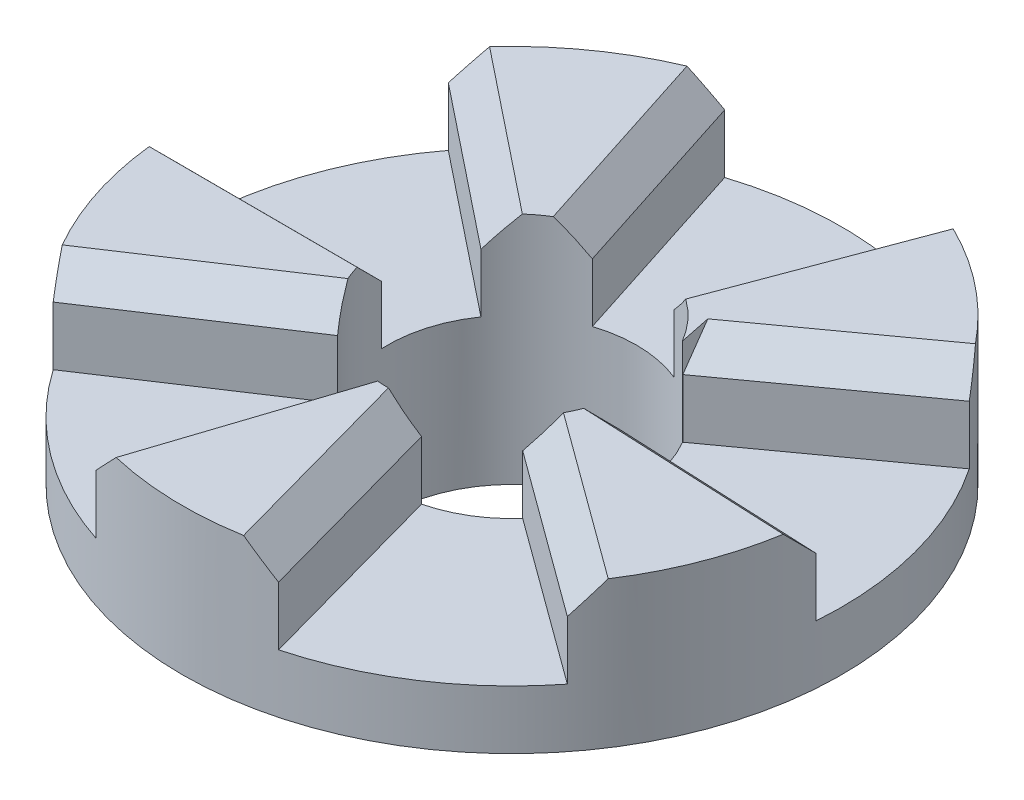
SolidWorks part; units mm, degrees
ref_plane "Front Plane" through (0, 0, 0) normal (0, 0, 1) x (1, 0, 0)
ref_plane "Top Plane" through (0, 0, 0) normal (0, 1, 0) x (1, 0, 0)
ref_plane "Right Plane" through (0, 0, 0) normal (1, 0, 0) x (0, 0, -1)
sketch "Sketch1" plane through (0, 0, 0) normal (0, 1, 0) x (1, 0, 0)
  circle A0 centre (0, 0) radius 11.25
  circle A1 centre (0, 0) radius 4.25
  dimension "D1" = 22.5
  dimension "D2" = 8.5
extrude "Boss-Extrude1" add sketch "Sketch1" along normal blind 5
sketch "Sketch3" plane through (0, 5, 0) normal (0, 1, 0) x (1, 0, 0)
  line L0 (-1.3024, 4.0455) -> (-3.4475, 10.7087)
  line L1 (1.5953, 3.9392) -> (4.0525, 10.4948)
  line L2 (3.6628, 2.1688) -> (9.4389, 6.3416)
  line L3 (4.2167, -0.5312) -> (11.553, -0.8575)
  line L4 (3.1821, -2.8172) -> (9.2675, -7.2637)
  line L5 (1.0349, -4.1221) -> (3.0742, -11.499)
  line L6 (-1.3402, -4.0331) -> (-3.7247, -11.305)
  line L7 (-3.3833, -2.5721) -> (-9.6666, -6.7235)
  line L8 (-4.2101, -0.2173) -> (-11.5831, -0.1974)
  line L9 (-3.488, 2.4282) -> (-9.062, 6.8694)
  line L10 (-1.3024, 4.0455) -> (1.5953, 3.9392)
  line L11 (3.6628, 2.1688) -> (4.2167, -0.5312)
  line L12 (3.1821, -2.8172) -> (1.0349, -4.1221)
  line L13 (-1.3402, -4.0331) -> (-3.3833, -2.5721)
  line L14 (-4.2101, -0.2173) -> (-3.488, 2.4282)
  line L15 (-3.4475, 10.7087) -> (-2.8145, 12.1133)
  line L16 (-2.8145, 12.1133) -> (3.474, 11.6818)
  line L17 (3.474, 11.6818) -> (4.0525, 10.4948)
  circle A0 centre (0, 0) radius 11.25 construction
  arc A2 (11.553, -0.8575) -> (9.4389, 6.3416) centre (-0.0098, -0.3432) ccw
  arc A3 (3.0742, -11.499) -> (9.2675, -7.2637) centre (-0.0098, -0.3432) ccw
  arc A4 (-9.6666, -6.7235) -> (-3.7247, -11.305) centre (-0.0098, -0.3432) ccw
  arc A5 (-9.062, 6.8694) -> (-11.5831, -0.1974) centre (-0.0098, -0.3432) ccw
  circle A6 centre (0, 0) radius 4.25 construction
  point P18 (-0.0098, -0.3432)
  dimension "D1" = 7.5
  dimension "D2" = 5
extrude "Cut-Extrude2" cut sketch "Sketch3" against normal blind 3
sketch "Sketch4" plane through (0, 0, 0) normal (0, -1, 0) x (1, 0, 0)
  circle A0 centre (0, 0) radius 4.25
  circle A1 centre (0, 0) radius 6.6208
extrude "Boss-Extrude2" add sketch "Sketch4" along normal blind 3
chamfer "Chamfer1" distance 1 angle 45 1 edges at (2.8239, 5, -7.217)
chamfer "Chamfer2" distance 1 angle 45 9 edges at (-2.375, 5, -7.3771) (-6.2275, 5, -4.611) (-7.7463, 5, 0.2078) (-6.3059, 5, 4.5031) (-2.4308, 5, 7.3589) (1.9675, 5, 7.4959) (6.0128, 5, 4.8855) (7.7175, 5, 0.6869) (6.5016, 5, -4.2196)
